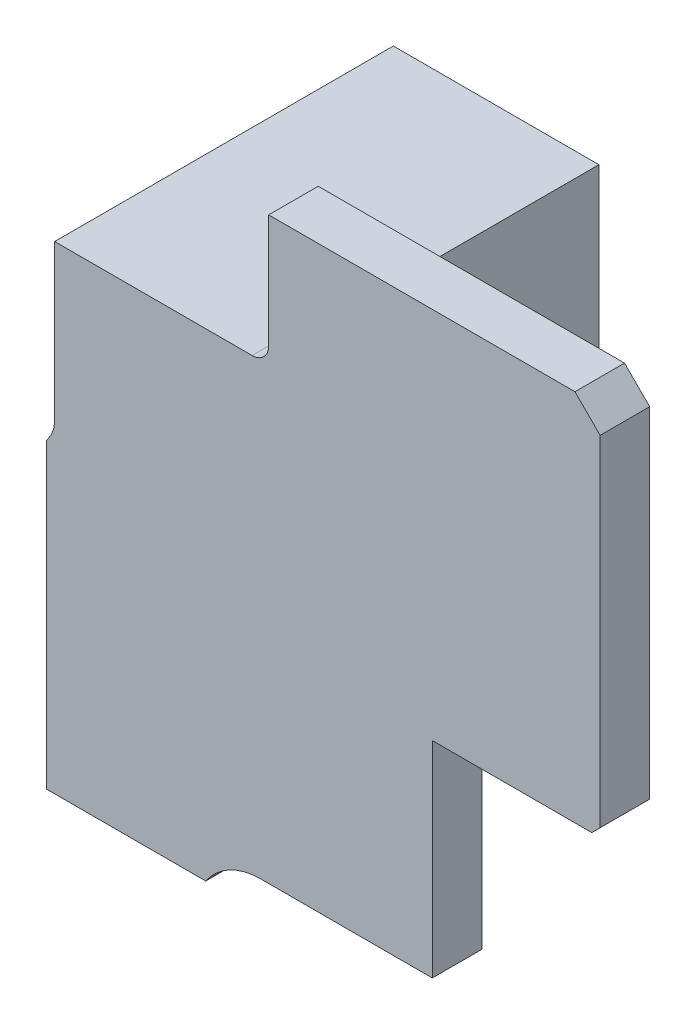
SolidWorks part; units mm, degrees
material "铜"
ref_plane "前视基准面" through (0, 0, 0) normal (0, 0, 1) x (1, 0, 0)
ref_plane "上视基准面" through (0, 0, 0) normal (0, 1, 0) x (1, 0, 0)
ref_plane "右视基准面" through (0, 0, 0) normal (1, 0, 0) x (0, 0, -1)
sketch "草图1" plane through (0, 0, 0) normal (0, 0, 1) x (1, 0, 0)
  line L0 (90.932, 85.09) -> (91.186, 85.344)
  line L1 (90.932, 75.946) -> (90.932, 85.09)
  line L2 (90.932, 75.946) -> (95.758, 75.946)
  line L6 (107.442, 83.058) -> (107.696, 83.312)
  line L7 (107.696, 83.312) -> (107.696, 93.599)
  line L8 (106.934, 94.361) -> (107.696, 93.599)
  line L9 (97.663, 94.361) -> (106.934, 94.361)
  line L10 (97.663, 90.9242) -> (97.663, 94.361)
  line L11 (97.1628, 90.424) -> (91.186, 90.424)
  line L12 (102.616, 83.058) -> (102.616, 76.8335)
  line L13 (91.186, 85.344) -> (91.186, 90.424)
  line L14 (95.758, 76.8335) -> (95.758, 75.946)
  line L15 (102.616, 83.058) -> (107.442, 83.058)
  line L16 (95.758, 76.8335) -> (102.616, 76.8335)
  arc A1 (97.663, 90.9242) -> (97.1628, 90.424) centre (97.1628, 90.9242) cw
  point P12 (102.616, 76.8335)
  point P13 (95.758, 76.8335)
extrude "凸台-拉伸1" add sketch "草图1" along normal blind 1.5 contours L13 L0 L1 L2 L6 L7 L8 L9 L10 region at (99.0239, 85.4048, 0)
sketch "草图2" plane through (0, 0, 0) normal (0, 0, 1) x (1, 0, 0)
  line L0 (90.932, 75.946) -> (90.932, 81.28)
  line L1 (90.932, 75.946) -> (95.25, 75.946)
  line L2 (95.25, 75.946) -> (95.25, 81.28)
  line L3 (90.932, 81.28) -> (95.25, 81.28)
extrude "凸台-拉伸2" add sketch "草图2" against normal blind 1.5 from surface starting at face at (98.8896, 85.294, 0)
sketch "草图3" plane through (0, 0, 0) normal (0, 0, 1) x (1, 0, 0)
  line L0 (97.409, 85.344) -> (97.409, 90.424)
  line L1 (91.186, 85.344) -> (97.409, 85.344)
  line L2 (91.186, 85.344) -> (91.186, 90.424)
  line L3 (91.186, 90.424) -> (97.409, 90.424)
extrude "凸台-拉伸3" add sketch "草图3" against normal blind 8.75 from surface starting at face at (98.4614, 84.8218, 0)
fillet "圆角1" radius 1 1 edges at (91.186, 85.344, 0.75)
fillet "圆角2" radius 2 1 edges at (95.758, 76.8335, 0.75)
